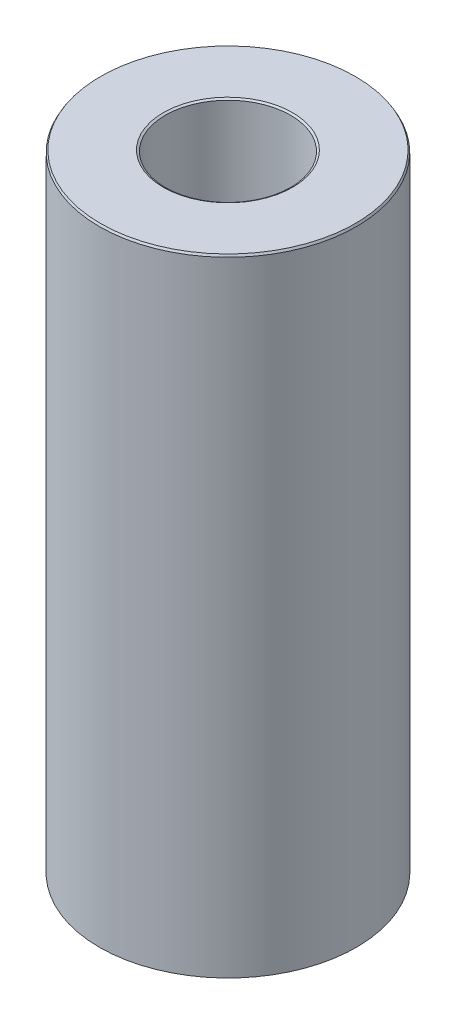
SolidWorks part; units mm, degrees
ref_plane "Front Plane" through (0, 0, 0) normal (0, 0, 1) x (1, 0, 0)
ref_plane "Top Plane" through (0, 0, 0) normal (0, 1, 0) x (1, 0, 0)
ref_plane "Right Plane" through (0, 0, 0) normal (1, 0, 0) x (0, 0, -1)
sketch "Sketch1" plane through (0, 0, 0) normal (0, 1, 0) x (1, 0, 0)
  circle A0 centre (0, 0) radius 50
  dimension "SLEEVE_OD" = 100
extrude "Boss-Extrude1" add sketch "Sketch1" along normal blind 244.0124
sketch "Sketch2" plane through (0, 0, 0) normal (0, 1, 0) x (1, 0, 0)
  circle A0 centre (0, 0) radius 24.3589
  dimension "BORE_D" = 48.7178
extrude "Cut-Extrude1" cut sketch "Sketch2" along normal through all
chamfer "Chamfer1" distance 0.7982 angle 30 4 edges at (0, 244.0124, 24.3589) (0, 0, 24.3589) (0, 0, 50) (0, 244.0124, 50) first distance on face at (0, 244.0124, 24.3589) first distance on face at (0, 0, 24.3589) first distance on face at (0, 244.0124, 50)
